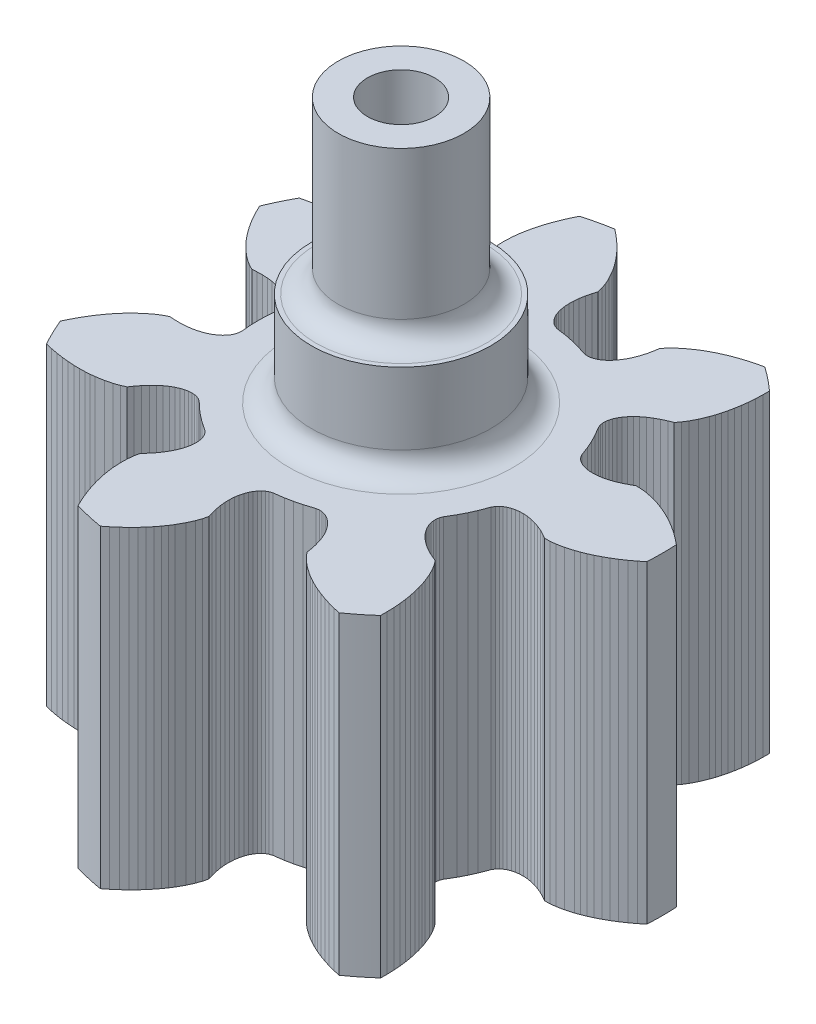
SolidWorks part; units mm, degrees
ref_plane "Front Plane" through (0, 0, 0) normal (0, 0, 1) x (1, 0, 0)
ref_plane "Top Plane" through (0, 0, 0) normal (0, 1, 0) x (1, 0, 0)
ref_plane "Right Plane" through (0, 0, 0) normal (1, 0, 0) x (0, 0, -1)
sketch "Sketch1" plane through (0, 0, 0) normal (0, 1, 0) x (1, 0, 0)
  circle A0 centre (0, 0) radius 2
  dimension "D1" = 4
extrude "Boss-Extrude1" add sketch "Sketch1" along normal blind 2.1
sketch "Sketch2" plane through (0, 2.1, 0) normal (0, 1, 0) x (1, 0, 0)
  circle A0 centre (0, 0) radius 1.4
  dimension "D1" = 2.8
extrude "Boss-Extrude3" add sketch "Sketch2" along normal blind 3.8
sketch "Sketch4" plane through (0, 0, 0) normal (0, -1, 0) x (1, 0, 0)
  line L420 (-1.6777, -5.4575) -> (-1.7402, -5.3144)
  line L421 (-1.7402, -5.3144) -> (-1.7939, -5.1757)
  line L422 (-1.7939, -5.1757) -> (-1.8392, -5.0423)
  line L423 (-1.8392, -5.0423) -> (-1.8764, -4.916)
  line L424 (-1.8764, -4.916) -> (-1.9071, -4.7932)
  line L425 (-1.9071, -4.7932) -> (-1.9311, -4.676)
  line L426 (-1.9311, -4.676) -> (-1.9488, -4.5668)
  line L427 (-1.9488, -4.5668) -> (-1.961, -4.464)
  line L428 (-1.961, -4.464) -> (-1.9715, -4.2798)
  line L429 (-1.9715, -4.2798) -> (-1.9674, -4.1246)
  line L430 (-1.9674, -4.1246) -> (-1.9537, -4.0009)
  line L431 (-1.9537, -4.0009) -> (-1.9303, -3.8867)
  line L432 (-1.9303, -3.8867) -> (-1.8594, -3.8097)
  line L433 (-1.8594, -3.8097) -> (-1.7784, -3.7125)
  line L434 (-1.7784, -3.7125) -> (-1.7087, -3.6155)
  line L435 (-1.7087, -3.6155) -> (-1.6501, -3.5195)
  line L436 (-1.6501, -3.5195) -> (-1.6023, -3.4251)
  line L437 (-1.6023, -3.4251) -> (-1.5652, -3.3333)
  line L438 (-1.5652, -3.3333) -> (-1.5384, -3.2446)
  line L439 (-1.5384, -3.2446) -> (-1.5215, -3.1597)
  line L440 (-1.5215, -3.1597) -> (-1.5143, -3.0795)
  line L441 (-1.5143, -3.0795) -> (-1.5162, -3.0043)
  line L442 (-1.5162, -3.0043) -> (-1.5269, -2.935)
  line L443 (-1.5269, -2.935) -> (-1.5457, -2.8721)
  line L444 (-1.5457, -2.8721) -> (-1.5723, -2.8162)
  line L445 (-1.5723, -2.8162) -> (-1.606, -2.7677)
  line L446 (-1.606, -2.7677) -> (-1.6572, -2.7183)
  line L447 (-1.6572, -2.7183) -> (-1.8447, -2.5928)
  line L448 (-1.8447, -2.5928) -> (-1.984, -2.4878)
  line L449 (-1.984, -2.4878) -> (-2.1173, -2.3754)
  line L450 (-2.1173, -2.3754) -> (-2.2814, -2.2205)
  line L451 (-2.2814, -2.2205) -> (-2.341, -2.1815)
  line L452 (-2.341, -2.1815) -> (-2.3957, -2.1595)
  line L453 (-2.3957, -2.1595) -> (-2.4562, -2.146)
  line L454 (-2.4562, -2.146) -> (-2.5217, -2.1417)
  line L455 (-2.5217, -2.1417) -> (-2.5917, -2.1467)
  line L456 (-2.5917, -2.1467) -> (-2.6653, -2.1615)
  line L457 (-2.6653, -2.1615) -> (-2.742, -2.1865)
  line L458 (-2.742, -2.1865) -> (-2.8209, -2.2218)
  line L459 (-2.8209, -2.2218) -> (-2.9014, -2.2676)
  line L460 (-2.9014, -2.2676) -> (-2.9827, -2.3243)
  line L461 (-2.9827, -2.3243) -> (-3.0641, -2.3918)
  line L462 (-3.0641, -2.3918) -> (-3.1447, -2.4703)
  line L463 (-3.1447, -2.4703) -> (-3.2237, -2.5599)
  line L464 (-3.2237, -2.5599) -> (-3.3005, -2.6605)
  line L465 (-3.3005, -2.6605) -> (-3.3598, -2.7467)
  line L466 (-3.3598, -2.7467) -> (-3.4659, -2.795)
  line L467 (-3.4659, -2.795) -> (-3.5835, -2.8358)
  line L468 (-3.5835, -2.8358) -> (-3.7338, -2.8744)
  line L469 (-3.7338, -2.8744) -> (-3.9158, -2.9052)
  line L470 (-3.9158, -2.9052) -> (-4.0187, -2.9161)
  line L471 (-4.0187, -2.9161) -> (-4.1291, -2.9232)
  line L472 (-4.1291, -2.9232) -> (-4.2487, -2.9258)
  line L473 (-4.2487, -2.9258) -> (-4.3752, -2.9233)
  line L474 (-4.3752, -2.9233) -> (-4.5067, -2.9151)
  line L475 (-4.5067, -2.9151) -> (-4.6468, -2.9006)
  line L476 (-4.6468, -2.9006) -> (-4.794, -2.8791)
  line L477 (-4.794, -2.8791) -> (-4.9474, -2.85)
  line L478 (-4.9474, -2.85) -> (-5.0902, -2.8167)
  line L479 (-5.3759, -2.2235) -> (-5.3129, -2.0911)
  line L480 (-5.3129, -2.0911) -> (-5.2399, -1.953)
  line L481 (-5.2399, -1.953) -> (-5.165, -1.8245)
  line L482 (-5.165, -1.8245) -> (-5.089, -1.7059)
  line L483 (-5.089, -1.7059) -> (-5.0134, -1.5981)
  line L484 (-5.0134, -1.5981) -> (-4.9365, -1.4976)
  line L485 (-4.9365, -1.4976) -> (-4.8599, -1.4057)
  line L486 (-4.8599, -1.4057) -> (-4.7855, -1.3238)
  line L487 (-4.7855, -1.3238) -> (-4.7128, -1.2502)
  line L488 (-4.7128, -1.2502) -> (-4.5753, -1.1271)
  line L489 (-4.5753, -1.1271) -> (-4.4514, -1.0336)
  line L490 (-4.4514, -1.0336) -> (-4.3462, -0.9671)
  line L491 (-4.3462, -0.9671) -> (-4.2422, -0.9142)
  line L492 (-4.2422, -0.9142) -> (-4.1379, -0.9217)
  line L493 (-4.1379, -0.9217) -> (-4.0114, -0.9244)
  line L494 (-4.0114, -0.9244) -> (-3.8921, -0.9184)
  line L495 (-3.8921, -0.9184) -> (-3.7804, -0.9043)
  line L496 (-3.7804, -0.9043) -> (-3.6769, -0.8828)
  line L497 (-3.6769, -0.8828) -> (-3.5819, -0.8546)
  line L498 (-3.5819, -0.8546) -> (-3.4959, -0.8203)
  line L499 (-3.4959, -0.8203) -> (-3.4191, -0.7805)
  line L500 (-3.4191, -0.7805) -> (-3.3518, -0.7361)
  line L501 (-3.3518, -0.7361) -> (-3.2942, -0.6878)
  line L502 (-3.2942, -0.6878) -> (-3.2467, -0.6363)
  line L503 (-3.2467, -0.6363) -> (-3.2093, -0.5823)
  line L504 (-3.2093, -0.5823) -> (-3.1821, -0.5267)
  line L505 (-3.1821, -0.5267) -> (-3.1652, -0.4701)
  line L506 (-3.1652, -0.4701) -> (-3.1585, -0.3992)
  line L507 (-3.1585, -0.3992) -> (-3.1773, -0.1744)
  line L508 (-3.1773, -0.1744) -> (-3.1821, 0)
  line L509 (-3.1821, 0) -> (-3.1773, 0.1743)
  line L510 (-3.1773, 0.1743) -> (-3.1585, 0.3991)
  line L511 (-3.1585, 0.3991) -> (-3.1652, 0.47)
  line L512 (-3.1652, 0.47) -> (-3.1821, 0.5266)
  line L513 (-3.1821, 0.5266) -> (-3.2093, 0.5822)
  line L514 (-3.2093, 0.5822) -> (-3.2467, 0.6362)
  line L515 (-3.2467, 0.6362) -> (-3.2942, 0.6877)
  line L516 (-3.2942, 0.6877) -> (-3.3518, 0.7361)
  line L517 (-3.3518, 0.7361) -> (-3.4191, 0.7805)
  line L518 (-3.4191, 0.7805) -> (-3.4959, 0.8202)
  line L519 (-3.4959, 0.8202) -> (-3.5819, 0.8545)
  line L520 (-3.5819, 0.8545) -> (-3.6769, 0.8828)
  line L521 (-3.6769, 0.8828) -> (-3.7804, 0.9043)
  line L522 (-3.7804, 0.9043) -> (-3.8921, 0.9183)
  line L523 (-3.8921, 0.9183) -> (-4.0114, 0.9243)
  line L524 (-4.0114, 0.9243) -> (-4.1379, 0.9216)
  line L525 (-4.1379, 0.9216) -> (-4.2422, 0.9142)
  line L526 (-4.2422, 0.9142) -> (-4.3462, 0.967)
  line L527 (-4.3462, 0.967) -> (-4.4514, 1.0335)
  line L528 (-4.4514, 1.0335) -> (-4.5753, 1.127)
  line L529 (-4.5753, 1.127) -> (-4.7128, 1.2501)
  line L530 (-4.7128, 1.2501) -> (-4.7855, 1.3238)
  line L531 (-4.7855, 1.3238) -> (-4.8599, 1.4056)
  line L532 (-4.8599, 1.4056) -> (-4.9365, 1.4975)
  line L533 (-4.9365, 1.4975) -> (-5.0134, 1.598)
  line L534 (-5.0134, 1.598) -> (-5.089, 1.7059)
  line L535 (-5.089, 1.7059) -> (-5.165, 1.8244)
  line L536 (-5.165, 1.8244) -> (-5.2399, 1.9529)
  line L537 (-5.2399, 1.9529) -> (-5.3129, 2.0911)
  line L538 (-5.3129, 2.0911) -> (-5.3759, 2.2234)
  line L539 (-5.0902, 2.8167) -> (-4.9474, 2.8499)
  line L540 (-4.9474, 2.8499) -> (-4.794, 2.879)
  line L541 (-4.794, 2.879) -> (-4.6468, 2.9005)
  line L542 (-4.6468, 2.9005) -> (-4.5067, 2.9151)
  line L543 (-4.5067, 2.9151) -> (-4.3752, 2.9232)
  line L544 (-4.3752, 2.9232) -> (-4.2487, 2.9257)
  line L545 (-4.2487, 2.9257) -> (-4.1291, 2.9231)
  line L546 (-4.1291, 2.9231) -> (-4.0187, 2.916)
  line L547 (-4.0187, 2.916) -> (-3.9158, 2.9051)
  line L548 (-3.9158, 2.9051) -> (-3.7338, 2.8743)
  line L549 (-3.7338, 2.8743) -> (-3.5835, 2.8358)
  line L550 (-3.5835, 2.8358) -> (-3.4659, 2.7949)
  line L551 (-3.4659, 2.7949) -> (-3.3598, 2.7466)
  line L552 (-3.3598, 2.7466) -> (-3.3005, 2.6604)
  line L553 (-3.3005, 2.6604) -> (-3.2237, 2.5598)
  line L554 (-3.2237, 2.5598) -> (-3.1447, 2.4703)
  line L555 (-3.1447, 2.4703) -> (-3.0641, 2.3918)
  line L556 (-3.0641, 2.3918) -> (-2.9827, 2.3242)
  line L557 (-2.9827, 2.3242) -> (-2.9014, 2.2676)
  line L558 (-2.9014, 2.2676) -> (-2.8209, 2.2217)
  line L559 (-2.8209, 2.2217) -> (-2.742, 2.1864)
  line L560 (-2.742, 2.1864) -> (-2.6653, 2.1615)
  line L561 (-2.6653, 2.1615) -> (-2.5917, 2.1466)
  line L562 (-2.5917, 2.1466) -> (-2.5217, 2.1416)
  line L563 (-2.5217, 2.1416) -> (-2.4562, 2.146)
  line L564 (-2.4562, 2.146) -> (-2.3957, 2.1594)
  line L565 (-2.3957, 2.1594) -> (-2.341, 2.1815)
  line L566 (-2.341, 2.1815) -> (-2.2814, 2.2205)
  line L567 (-2.2814, 2.2205) -> (-2.1173, 2.3753)
  line L568 (-2.1173, 2.3753) -> (-1.984, 2.4878)
  line L569 (-1.984, 2.4878) -> (-1.8447, 2.5927)
  line L570 (-1.8447, 2.5927) -> (-1.6572, 2.7182)
  line L571 (-1.6572, 2.7182) -> (-1.606, 2.7676)
  line L572 (-1.606, 2.7676) -> (-1.5723, 2.8161)
  line L573 (-1.5723, 2.8161) -> (-1.5457, 2.8721)
  line L574 (-1.5457, 2.8721) -> (-1.5269, 2.935)
  line L575 (-1.5269, 2.935) -> (-1.5162, 3.0043)
  line L576 (-1.5162, 3.0043) -> (-1.5143, 3.0794)
  line L577 (-1.5143, 3.0794) -> (-1.5215, 3.1597)
  line L578 (-1.5215, 3.1597) -> (-1.5384, 3.2445)
  line L579 (-1.5384, 3.2445) -> (-1.5652, 3.3332)
  line L580 (-1.5652, 3.3332) -> (-1.6023, 3.4251)
  line L581 (-1.6023, 3.4251) -> (-1.6501, 3.5194)
  line L582 (-1.6501, 3.5194) -> (-1.7087, 3.6154)
  line L583 (-1.7087, 3.6154) -> (-1.7784, 3.7125)
  line L584 (-1.7784, 3.7125) -> (-1.8594, 3.8097)
  line L585 (-1.8594, 3.8097) -> (-1.9303, 3.8866)
  line L586 (-1.9303, 3.8866) -> (-1.9537, 4.0009)
  line L587 (-1.9537, 4.0009) -> (-1.9674, 4.1246)
  line L588 (-1.9674, 4.1246) -> (-1.9715, 4.2797)
  line L589 (-1.9715, 4.2797) -> (-1.961, 4.464)
  line L590 (-1.961, 4.464) -> (-1.9488, 4.5668)
  line L591 (-1.9488, 4.5668) -> (-1.9311, 4.6759)
  line L592 (-1.9311, 4.6759) -> (-1.9071, 4.7932)
  line L593 (-1.9071, 4.7932) -> (-1.8764, 4.9159)
  line L594 (-1.8764, 4.9159) -> (-1.8392, 5.0423)
  line L595 (-1.8392, 5.0423) -> (-1.7939, 5.1756)
  line L596 (-1.7939, 5.1756) -> (-1.7402, 5.3143)
  line L597 (-1.7402, 5.3143) -> (-1.6777, 5.4575)
  line L598 (-1.6777, 5.4575) -> (-1.6135, 5.5893)
  line L599 (-0.9715, 5.7358) -> (-0.8565, 5.6449)
  line L600 (-0.8565, 5.6449) -> (-0.7381, 5.543)
  line L601 (-0.7381, 5.543) -> (-0.6295, 5.4414)
  line L602 (-0.6295, 5.4414) -> (-0.5308, 5.3409)
  line L603 (-0.5308, 5.3409) -> (-0.4425, 5.2432)
  line L604 (-0.4425, 5.2432) -> (-0.3616, 5.1459)
  line L605 (-0.3616, 5.1459) -> (-0.2891, 5.0507)
  line L606 (-0.2891, 5.0507) -> (-0.2258, 4.96)
  line L607 (-0.2258, 4.96) -> (-0.1702, 4.8727)
  line L608 (-0.1702, 4.8727) -> (-0.0808, 4.7113)
  line L609 (-0.0808, 4.7113) -> (-0.0172, 4.5697)
  line L610 (-0.0172, 4.5697) -> (0.0242, 4.4523)
  line L611 (0.0242, 4.4523) -> (0.0526, 4.3392)
  line L612 (0.0526, 4.3392) -> (0.0222, 4.2391)
  line L613 (0.0222, 4.2391) -> (-0.0086, 4.1164)
  line L614 (-0.0086, 4.1164) -> (-0.0293, 3.9987)
  line L615 (-0.0293, 3.9987) -> (-0.0405, 3.8868)
  line L616 (-0.0405, 3.8868) -> (-0.0426, 3.7811)
  line L617 (-0.0426, 3.7811) -> (-0.0362, 3.6822)
  line L618 (-0.0362, 3.6822) -> (-0.0218, 3.5907)
  line L619 (-0.0218, 3.5907) -> (-0.0002, 3.5069)
  line L620 (-0.0002, 3.5069) -> (0.0281, 3.4314)
  line L621 (0.0281, 3.4314) -> (0.0624, 3.3646)
  line L622 (0.0624, 3.3646) -> (0.1021, 3.3068)
  line L623 (0.1021, 3.3068) -> (0.1464, 3.2583)
  line L624 (0.1464, 3.2583) -> (0.1946, 3.2194)
  line L625 (0.1946, 3.2194) -> (0.246, 3.1903)
  line L626 (0.246, 3.1903) -> (0.3136, 3.1681)
  line L627 (0.3136, 3.1681) -> (0.537, 3.1363)
  line L628 (0.537, 3.1363) -> (0.708, 3.1022)
  line L629 (0.708, 3.1022) -> (0.8769, 3.0588)
  line L630 (0.8769, 3.0588) -> (1.0919, 2.9904)
  line L631 (1.0919, 2.9904) -> (1.1625, 2.9811)
  line L632 (1.1625, 2.9811) -> (1.2214, 2.985)
  line L633 (1.2214, 2.985) -> (1.2817, 2.9991)
  line L634 (1.2817, 2.9991) -> (1.3427, 3.0236)
  line L635 (1.3427, 3.0236) -> (1.4035, 3.0585)
  line L636 (1.4035, 3.0585) -> (1.4634, 3.1038)
  line L637 (1.4634, 3.1038) -> (1.5217, 3.1596)
  line L638 (1.5217, 3.1596) -> (1.5775, 3.2256)
  line L639 (1.5775, 3.2256) -> (1.6301, 3.3019)
  line L640 (1.6301, 3.3019) -> (1.6788, 3.3882)
  line L641 (1.6788, 3.3882) -> (1.7228, 3.4843)
  line L642 (1.7228, 3.4843) -> (1.7613, 3.59)
  line L643 (1.7613, 3.59) -> (1.7937, 3.705)
  line L644 (1.7937, 3.705) -> (1.8192, 3.829)
  line L645 (1.8192, 3.829) -> (1.8352, 3.9324)
  line L646 (1.8352, 3.9324) -> (1.9099, 4.0219)
  line L647 (1.9099, 4.0219) -> (1.9981, 4.1097)
  line L648 (1.9981, 4.1097) -> (2.1168, 4.2097)
  line L649 (2.1168, 4.2097) -> (2.2674, 4.3164)
  line L650 (2.2674, 4.3164) -> (2.3554, 4.3709)
  line L651 (2.3554, 4.3709) -> (2.4518, 4.4251)
  line L652 (2.4518, 4.4251) -> (2.5584, 4.4794)
  line L653 (2.5584, 4.4794) -> (2.6735, 4.532)
  line L654 (2.6735, 4.532) -> (2.7955, 4.5817)
  line L655 (2.7955, 4.5817) -> (2.928, 4.6294)
  line L656 (2.928, 4.6294) -> (3.0699, 4.6739)
  line L657 (3.0699, 4.6739) -> (3.2208, 4.7143)
  line L658 (3.2208, 4.7143) -> (3.3639, 4.7463)
  line L659 (3.8787, 4.3357) -> (3.8793, 4.1891)
  line L660 (3.8793, 4.1891) -> (3.8735, 4.033)
  line L661 (3.8735, 4.033) -> (3.8618, 3.8847)
  line L662 (3.8618, 3.8847) -> (3.8448, 3.7449)
  line L663 (3.8448, 3.7449) -> (3.8234, 3.615)
  line L664 (3.8234, 3.615) -> (3.7978, 3.4911)
  line L665 (3.7978, 3.4911) -> (3.7686, 3.375)
  line L666 (3.7686, 3.375) -> (3.7371, 3.269)
  line L667 (3.7371, 3.269) -> (3.7036, 3.1711)
  line L668 (3.7036, 3.1711) -> (3.6331, 3.0005)
  line L669 (3.6331, 3.0005) -> (3.562, 2.8625)
  line L670 (3.562, 2.8625) -> (3.4961, 2.757)
  line L671 (3.4961, 2.757) -> (3.4253, 2.6643)
  line L672 (3.4253, 2.6643) -> (3.3281, 2.6257)
  line L673 (3.3281, 2.6257) -> (3.213, 2.5732)
  line L674 (3.213, 2.5732) -> (3.1081, 2.516)
  line L675 (3.1081, 2.516) -> (3.0136, 2.4549)
  line L676 (3.0136, 2.4549) -> (2.9296, 2.3907)
  line L677 (2.9296, 2.3907) -> (2.8563, 2.324)
  line L678 (2.8563, 2.324) -> (2.7937, 2.2557)
  line L679 (2.7937, 2.2557) -> (2.7417, 2.1866)
  line L680 (2.7417, 2.1866) -> (2.7003, 2.1174)
  line L681 (2.7003, 2.1174) -> (2.6695, 2.0489)
  line L682 (2.6695, 2.0489) -> (2.649, 1.9819)
  line L683 (2.649, 1.9819) -> (2.6387, 1.917)
  line L684 (2.6387, 1.917) -> (2.6383, 1.8551)
  line L685 (2.6383, 1.8551) -> (2.6476, 1.7967)
  line L686 (2.6476, 1.7967) -> (2.6724, 1.73)
  line L687 (2.6724, 1.73) -> (2.7869, 1.5356)
  line L688 (2.7869, 1.5356) -> (2.8668, 1.3806)
  line L689 (2.8668, 1.3806) -> (2.9382, 1.2215)
  line L690 (2.9382, 1.2215) -> (3.0188, 1.0107)
  line L691 (3.0188, 1.0107) -> (3.0555, 0.9498)
  line L692 (3.0555, 0.9498) -> (3.0953, 0.9061)
  line L693 (3.0953, 0.9061) -> (3.144, 0.8678)
  line L694 (3.144, 0.8678) -> (3.2011, 0.8354)
  line L695 (3.2011, 0.8354) -> (3.2663, 0.8096)
  line L696 (3.2663, 0.8096) -> (3.3391, 0.791)
  line L697 (3.3391, 0.791) -> (3.419, 0.7802)
  line L698 (3.419, 0.7802) -> (3.5054, 0.7777)
  line L699 (3.5054, 0.7777) -> (3.5979, 0.7842)
  line L700 (3.5979, 0.7842) -> (3.6957, 0.7999)
  line L701 (3.6957, 0.7999) -> (3.7983, 0.8255)
  line L702 (3.7983, 0.8255) -> (3.905, 0.8612)
  line L703 (3.905, 0.8612) -> (4.0151, 0.9076)
  line L704 (4.0151, 0.9076) -> (4.1279, 0.9649)
  line L705 (4.1279, 0.9649) -> (4.2187, 1.0169)
  line L706 (4.2187, 1.0169) -> (4.3353, 1.0144)
  line L707 (4.3353, 1.0144) -> (4.4589, 1.0001)
  line L708 (4.4589, 1.0001) -> (4.6111, 0.9696)
  line L709 (4.6111, 0.9696) -> (4.7884, 0.9184)
  line L710 (4.7884, 0.9184) -> (4.8859, 0.8836)
  line L711 (4.8859, 0.8836) -> (4.9884, 0.8421)
  line L712 (4.9884, 0.8421) -> (5.0973, 0.7926)
  line L713 (5.0973, 0.7926) -> (5.2102, 0.7354)
  line L714 (5.2102, 0.7354) -> (5.3251, 0.671)
  line L715 (5.3251, 0.671) -> (5.445, 0.5972)
  line L716 (5.445, 0.5972) -> (5.5683, 0.5139)
  line L717 (5.5683, 0.5139) -> (5.6939, 0.4211)
  line L718 (5.6939, 0.4211) -> (5.8081, 0.3292)
  line L719 (5.8081, -0.3293) -> (5.6939, -0.4212)
  line L720 (5.6939, -0.4212) -> (5.5683, -0.514)
  line L721 (5.5683, -0.514) -> (5.445, -0.5972)
  line L722 (5.445, -0.5972) -> (5.3251, -0.6711)
  line L723 (5.3251, -0.6711) -> (5.2102, -0.7354)
  line L724 (5.2102, -0.7354) -> (5.0973, -0.7926)
  line L725 (5.0973, -0.7926) -> (4.9884, -0.8421)
  line L726 (4.9884, -0.8421) -> (4.8859, -0.8837)
  line L727 (4.8859, -0.8837) -> (4.7884, -0.9185)
  line L728 (4.7884, -0.9185) -> (4.6111, -0.9697)
  line L729 (4.6111, -0.9697) -> (4.4589, -1.0002)
  line L730 (4.4589, -1.0002) -> (4.3353, -1.0144)
  line L731 (4.3353, -1.0144) -> (4.2187, -1.017)
  line L732 (4.2187, -1.017) -> (4.1279, -0.965)
  line L733 (4.1279, -0.965) -> (4.0151, -0.9077)
  line L734 (4.0151, -0.9077) -> (3.905, -0.8613)
  line L735 (3.905, -0.8613) -> (3.7983, -0.8255)
  line L736 (3.7983, -0.8255) -> (3.6957, -0.8)
  line L737 (3.6957, -0.8) -> (3.5979, -0.7842)
  line L738 (3.5979, -0.7842) -> (3.5054, -0.7778)
  line L739 (3.5054, -0.7778) -> (3.419, -0.7803)
  line L740 (3.419, -0.7803) -> (3.3391, -0.7911)
  line L741 (3.3391, -0.7911) -> (3.2663, -0.8097)
  line L742 (3.2663, -0.8097) -> (3.2011, -0.8354)
  line L743 (3.2011, -0.8354) -> (3.144, -0.8678)
  line L744 (3.144, -0.8678) -> (3.0953, -0.9062)
  line L745 (3.0953, -0.9062) -> (3.0555, -0.9498)
  line L746 (3.0555, -0.9498) -> (3.0188, -1.0108)
  line L747 (3.0188, -1.0108) -> (2.9382, -1.2215)
  line L748 (2.9382, -1.2215) -> (2.8668, -1.3806)
  line L749 (2.8668, -1.3806) -> (2.7869, -1.5356)
  line L750 (2.7869, -1.5356) -> (2.6724, -1.7301)
  line L751 (2.6724, -1.7301) -> (2.6476, -1.7968)
  line L752 (2.6476, -1.7968) -> (2.6383, -1.8551)
  line L753 (2.6383, -1.8551) -> (2.6387, -1.9171)
  line L754 (2.6387, -1.9171) -> (2.649, -1.9819)
  line L755 (2.649, -1.9819) -> (2.6695, -2.049)
  line L756 (2.6695, -2.049) -> (2.7003, -2.1175)
  line L757 (2.7003, -2.1175) -> (2.7417, -2.1867)
  line L758 (2.7417, -2.1867) -> (2.7937, -2.2558)
  line L759 (2.7937, -2.2558) -> (2.8563, -2.3241)
  line L760 (2.8563, -2.3241) -> (2.9296, -2.3907)
  line L761 (2.9296, -2.3907) -> (3.0136, -2.455)
  line L762 (3.0136, -2.455) -> (3.1081, -2.5161)
  line L763 (3.1081, -2.5161) -> (3.213, -2.5733)
  line L764 (3.213, -2.5733) -> (3.3281, -2.6257)
  line L765 (3.3281, -2.6257) -> (3.4253, -2.6643)
  line L766 (3.4253, -2.6643) -> (3.4961, -2.757)
  line L767 (3.4961, -2.757) -> (3.562, -2.8626)
  line L768 (3.562, -2.8626) -> (3.6331, -3.0006)
  line L769 (3.6331, -3.0006) -> (3.7036, -3.1711)
  line L770 (3.7036, -3.1711) -> (3.7371, -3.2691)
  line L771 (3.7371, -3.2691) -> (3.7686, -3.3751)
  line L772 (3.7686, -3.3751) -> (3.7978, -3.4911)
  line L773 (3.7978, -3.4911) -> (3.8234, -3.615)
  line L774 (3.8234, -3.615) -> (3.8448, -3.745)
  line L775 (3.8448, -3.745) -> (3.8618, -3.8848)
  line L776 (3.8618, -3.8848) -> (3.8735, -4.0331)
  line L777 (3.8735, -4.0331) -> (3.8793, -4.1892)
  line L778 (3.8793, -4.1892) -> (3.8787, -4.3358)
  line L779 (3.3639, -4.7463) -> (3.2208, -4.7143)
  line L780 (3.2208, -4.7143) -> (3.0699, -4.6739)
  line L781 (3.0699, -4.6739) -> (2.928, -4.6295)
  line L782 (2.928, -4.6295) -> (2.7955, -4.5818)
  line L783 (2.7955, -4.5818) -> (2.6735, -4.5321)
  line L784 (2.6735, -4.5321) -> (2.5584, -4.4795)
  line L785 (2.5584, -4.4795) -> (2.4518, -4.4252)
  line L786 (2.4518, -4.4252) -> (2.3554, -4.3709)
  line L787 (2.3554, -4.3709) -> (2.2674, -4.3164)
  line L788 (2.2674, -4.3164) -> (2.1168, -4.2097)
  line L789 (2.1168, -4.2097) -> (1.9981, -4.1098)
  line L790 (1.9981, -4.1098) -> (1.9099, -4.022)
  line L791 (1.9099, -4.022) -> (1.8352, -3.9324)
  line L792 (1.8352, -3.9324) -> (1.8192, -3.829)
  line L793 (1.8192, -3.829) -> (1.7937, -3.7051)
  line L794 (1.7937, -3.7051) -> (1.7613, -3.5901)
  line L795 (1.7613, -3.5901) -> (1.7228, -3.4844)
  line L796 (1.7228, -3.4844) -> (1.6788, -3.3883)
  line L797 (1.6788, -3.3883) -> (1.6301, -3.3019)
  line L798 (1.6301, -3.3019) -> (1.5775, -3.2257)
  line L799 (1.5775, -3.2257) -> (1.5217, -3.1596)
  line L800 (1.5217, -3.1596) -> (1.4634, -3.1039)
  line L801 (1.4634, -3.1039) -> (1.4035, -3.0586)
  line L802 (1.4035, -3.0586) -> (1.3427, -3.0237)
  line L803 (1.3427, -3.0237) -> (1.2817, -2.9992)
  line L804 (1.2817, -2.9992) -> (1.2214, -2.9851)
  line L805 (1.2214, -2.9851) -> (1.1625, -2.9812)
  line L806 (1.1625, -2.9812) -> (1.0919, -2.9905)
  line L807 (1.0919, -2.9905) -> (0.8769, -3.0588)
  line L808 (0.8769, -3.0588) -> (0.708, -3.1023)
  line L809 (0.708, -3.1023) -> (0.537, -3.1364)
  line L810 (0.537, -3.1364) -> (0.3136, -3.1681)
  line L811 (0.3136, -3.1681) -> (0.246, -3.1904)
  line L812 (0.246, -3.1904) -> (0.1946, -3.2194)
  line L813 (0.1946, -3.2194) -> (0.1464, -3.2583)
  line L814 (0.1464, -3.2583) -> (0.1021, -3.3068)
  line L815 (0.1021, -3.3068) -> (0.0624, -3.3647)
  line L816 (0.0624, -3.3647) -> (0.0281, -3.4315)
  line L817 (0.0281, -3.4315) -> (-0.0002, -3.507)
  line L818 (-0.0002, -3.507) -> (-0.0218, -3.5907)
  line L819 (-0.0218, -3.5907) -> (-0.0362, -3.6823)
  line L820 (-0.0362, -3.6823) -> (-0.0426, -3.7811)
  line L821 (-0.0426, -3.7811) -> (-0.0405, -3.8868)
  line L822 (-0.0405, -3.8868) -> (-0.0293, -3.9988)
  line L823 (-0.0293, -3.9988) -> (-0.0086, -4.1165)
  line L824 (-0.0086, -4.1165) -> (0.0222, -4.2392)
  line L825 (0.0222, -4.2392) -> (0.0526, -4.3393)
  line L826 (0.0526, -4.3393) -> (0.0242, -4.4524)
  line L827 (0.0242, -4.4524) -> (-0.0172, -4.5698)
  line L828 (-0.0172, -4.5698) -> (-0.0808, -4.7113)
  line L829 (-0.0808, -4.7113) -> (-0.1702, -4.8728)
  line L830 (-0.1702, -4.8728) -> (-0.2258, -4.9601)
  line L831 (-0.2258, -4.9601) -> (-0.2891, -5.0508)
  line L832 (-0.2891, -5.0508) -> (-0.3616, -5.146)
  line L833 (-0.3616, -5.146) -> (-0.4425, -5.2433)
  line L834 (-0.4425, -5.2433) -> (-0.5308, -5.341)
  line L835 (-0.5308, -5.341) -> (-0.6295, -5.4414)
  line L836 (-0.6295, -5.4414) -> (-0.7381, -5.5431)
  line L837 (-0.7381, -5.5431) -> (-0.8565, -5.645)
  line L838 (-0.8565, -5.645) -> (-0.9715, -5.7359)
  line L839 (-1.6135, -5.5894) -> (-1.6777, -5.4575)
  arc A7 (-5.3759, -2.2235) -> (-5.0902, -2.8167) centre (0, 0) ccw
  arc A8 (-5.0902, 2.8167) -> (-5.3759, 2.2234) centre (0, -0.0001) ccw
  arc A9 (-0.9715, 5.7358) -> (-1.6135, 5.5893) centre (0, -0.0001) ccw
  arc A10 (3.8787, 4.3357) -> (3.3639, 4.7463) centre (-0.0001, -0.0001) ccw
  arc A11 (5.8081, -0.3293) -> (5.8081, 0.3292) centre (-0.0001, 0) ccw
  arc A12 (3.3639, -4.7463) -> (3.8787, -4.3358) centre (-0.0001, 0) ccw
  arc A13 (-1.6135, -5.5894) -> (-0.9715, -5.7359) centre (0, 0) ccw
extrude "Boss-Extrude4" add sketch "Sketch4" along normal blind 7
sketch "Sketch3" plane through (0, 0, 0) normal (0, -1, 0) x (1, 0, 0)
  circle A0 centre (0, 0) radius 1.1
  circle A1 centre (0, 0) radius 0.75
  dimension "D1" = 2.2
  dimension "D2" = 1.5
extrude "Cut-Extrude1" cut sketch "Sketch3" against normal through all contours A1
extrude "Cut-Extrude2" cut sketch "Sketch3<3>" along normal through all contours A0 A1 | A1 region at (-1.0689, 0, 0) region at (0, 0, 0)
sketch "Sketch3<3>" plane through (0, 0, 0) normal (0, -1, 0) x (1, 0, 0) same geometry as "Sketch3"
fillet "Fillet1" radius 0.5 2 edges at (0, 2.1, 1.4) (0, 0, -2)
chamfer "Chamfer1" distance 0.4 angle 45 2 edges at (0, 0, 1.1) (0, -7, 1.1)
